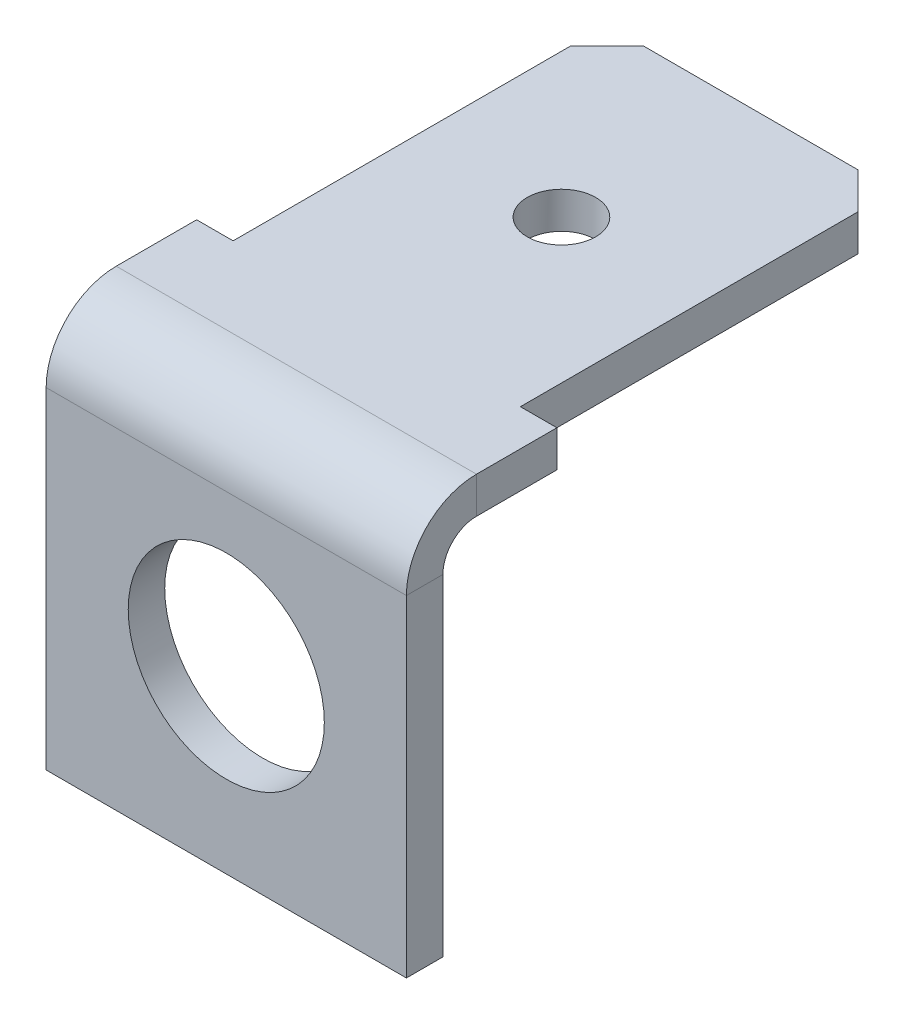
SolidWorks part; units mm, degrees
note: The reader was unsure of these and kept them because the rebuilt part matched: flange length of "边线-法兰1".
ref_plane "前视基准面" through (0, 0, 0) normal (0, 0, 1) x (1, 0, 0)
ref_plane "上视基准面" through (0, 0, 0) normal (0, 1, 0) x (1, 0, 0)
ref_plane "右视基准面" through (0, 0, 0) normal (1, 0, 0) x (0, 0, -1)
sketch "草图1" plane through (0, 0, 0) normal (0, 0, 1) x (1, 0, 0)
  line L0 (0, -9.6598) -> (0, 15.7475) construction
  line L1 (-3.95, 4.4) -> (3.95, 4.4)
  line L2 (-3.95, 4.4) -> (-3.95, -4.4)
  line L3 (-3.95, -4.4) -> (3.95, -4.4)
  line L4 (3.95, 4.4) -> (3.95, -4.4)
  line L5 (-7.2033, 0) -> (10.3863, 0) construction
  dimension "D1" = 8.8
  dimension "D2" = 7.9
sheet metal parameters "钣金1" thickness 0.8 parameters "D1"=0.7366
base flange "基体-法兰1" sketch "草图1" thickness 0.8 reverse thickness direction no parameters "D1"=0.7366
edge flange "边线-法兰1" sketch "草图6" flange angle 90 flange length 11.5 flange position material inside bend radius 0.7366 thickness 0.8 relief rectangular parameters "D6"=10
sketch "草图6" plane through (0, 4.4, -0.8) normal (0, 1, 0) x (1, 0, 0)
  line L0 (3.95, 0) -> (-3.95, 0) construction
  line L1 (3.95, 0) -> (-3.95, 0)
  line L2 (-3.95, 0) -> (-3.95, 10.7)
  line L3 (-3.95, 10.7) -> (3.95, 10.7)
  line L4 (3.95, 10.7) -> (3.95, 0)
bend "边线折弯1" bend radius 0.7366 bend angle 90 parameters "D5"=1
sketch "草图7" plane through (0, 0, -0.8) normal (0, 0, -1) x (-1, 0, 0)
  line L0 (-4.184, -0.45) -> (5.451, -0.45) construction
  line L3 (0, 1.5519) -> (0, -4.6811) construction
  line L4 (3.95, -4.4) -> (-3.95, -4.4) construction
  circle A0 centre (0, -0.45) radius 2.15
  dimension "D1" = 4.3
  dimension "D2" = 3.95
extrude "切除-拉伸1" cut sketch "草图7" against normal blind 10 normal cut yes
sketch "草图8" plane through (0, 4.4, 0) normal (0, 1, 0) x (1, 0, 0)
  line L0 (0, -1.6347) -> (0, 10.6777) construction
  line L2 (3.15, 11.5) -> (3.15, 3.3)
  line L3 (-3.95, 11.5) -> (-3.15, 11.5)
  line L4 (-3.95, 11.5) -> (-3.95, 3.3)
  line L5 (-3.95, 3.3) -> (-3.15, 3.3)
  line L6 (-3.15, 11.5) -> (-3.15, 3.3)
  line L7 (3.95, 3.3) -> (3.15, 3.3)
  line L8 (3.95, 11.5) -> (3.95, 3.3)
  line L9 (3.95, 11.5) -> (3.15, 11.5)
  dimension "D1" = 8.2
  dimension "D2" = 6.3
extrude "切除-拉伸2" cut sketch "草图8" against normal blind 10 normal cut yes
sketch "草图9" plane through (0, 4.4, 0) normal (0, 1, 0) x (1, 0, 0)
  line L0 (0, -2.4042) -> (0, 11.8617) construction
  line L1 (3.15, 11.5) -> (-3.15, 11.5) construction
  circle A0 centre (0, 7.35) radius 0.75
  dimension "D1" = 1.5
  dimension "D2" = 4.15
extrude "切除-拉伸3" cut sketch "草图9" against normal blind 10 normal cut yes
chamfer "倒角1" distance 0.8 angle 45 2 edges at (3.15, 4, -11.5) (-3.15, 4, -11.5)
flat pattern "平板型式1" [suppressed]
sketch "折弯-线1" plane through (0, 0, 0) normal (0, 1, 0) x (1, 0, 0)
sketch3d "边界框1" [suppressed]
  line L0 (-2.5, 3.5, 0) -> (-2.5, -3.5, 0) construction
  line L1 (2.5, 3.5, 0) -> (2.5, -3.5, 0) construction
  line L2 (-2.5, 3.5, 0) -> (2.5, 3.5, 0) construction
  line L3 (-2.5, -3.5, 0) -> (2.5, -3.5, 0) construction
bend of the flat pattern "展开-<边线折弯1>1"
